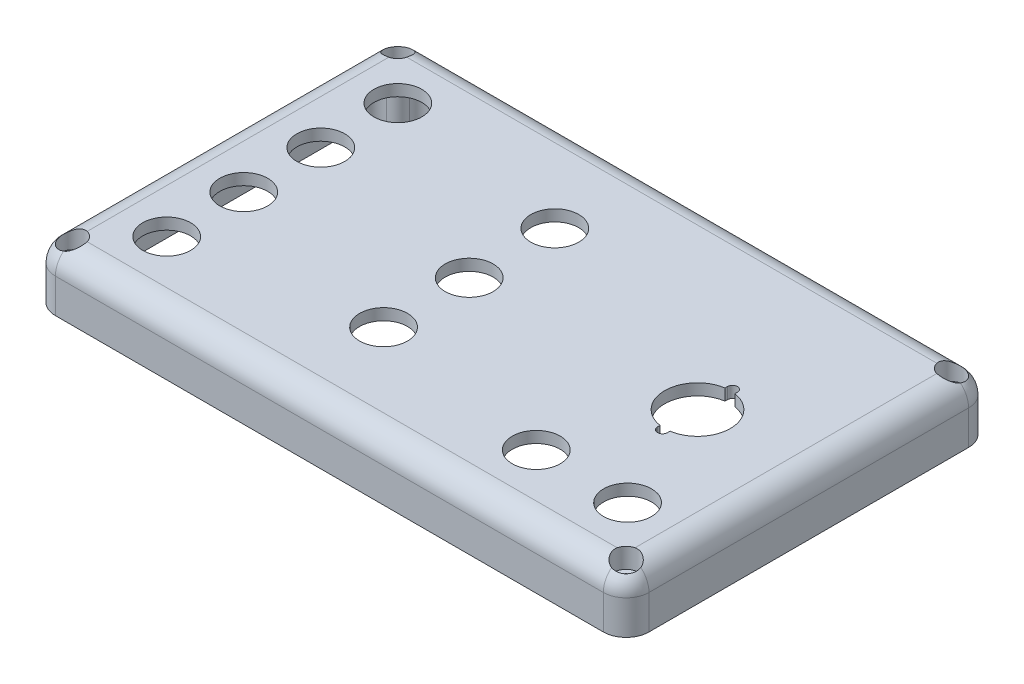
SolidWorks part; units mm, degrees
ref_plane "Front Plane" through (0, 0, 0) normal (0, 0, 1) x (1, 0, 0)
ref_plane "Top Plane" through (0, 0, 0) normal (0, 1, 0) x (1, 0, 0)
ref_plane "Right Plane" through (0, 0, 0) normal (1, 0, 0) x (0, 0, -1)
sketch "Sketch1" plane through (0, 0, 0) normal (0, 1, 0) x (1, 0, 0)
  line L0 (0, 112) -> (8, 112)
  line L1 (0, 0) -> (200, 0)
  line L2 (0, 0) -> (0, 120)
  line L3 (0, 120) -> (200, 120)
  line L4 (200, 0) -> (200, 120)
  line L5 (-4, 124) -> (204, 124)
  line L6 (-4, 124) -> (-4, -4)
  line L7 (-4, -4) -> (204, -4)
  line L8 (204, 124) -> (204, -4)
  line L9 (8, 112) -> (8, 120)
  line L10 (100, 120) -> (100, 0) construction
  line L11 (0, 60) -> (200, 60) construction
  line L12 (192, 112) -> (192, 120)
  line L13 (200, 112) -> (192, 112)
  line L14 (200, 8) -> (192, 8)
  line L15 (192, 8) -> (192, 0)
  line L16 (8, 8) -> (8, 0)
  line L17 (0, 8) -> (8, 8)
  line L18 (165, 60) -> (165, 0) construction
  line L19 (163.25, 71.3661) -> (163.25, 72.25)
  line L20 (166.75, 72.25) -> (166.75, 71.3661)
  line L21 (163.25, 48.6339) -> (163.25, 47.75)
  line L22 (166.75, 47.75) -> (166.75, 48.6339)
  circle A0 centre (19.5, 100.5) radius 8.4
  circle A1 centre (19.5, 73.5) radius 8.4
  circle A2 centre (19.5, 46.5) radius 8.4
  circle A3 centre (19.5, 19.5) radius 8.4
  circle A4 centre (85, 90) radius 8.4
  circle A5 centre (85, 60) radius 8.4
  circle A6 centre (85, 30) radius 8.4
  circle A9 centre (165, 60) radius 11.5
  circle A10 centre (149, 19.5) radius 8.4
  circle A11 centre (181, 19.5) radius 8.4
  circle A12 centre (165, 60) radius 16 construction
  arc A13 (163.25, 72.25) -> (166.75, 72.25) centre (165, 72.25) cw
  arc A14 (163.25, 47.75) -> (166.75, 47.75) centre (165, 47.75) ccw
  point P51 (165, 74)
  point P54 (165, 71.5)
  dimension "D9" = 16.8
  dimension "D13" = 16.8
  dimension "D19" = 23
  dimension "D21" = 16.8
  dimension "D22" = 32
  dimension "D1" = 200
  dimension "D2" = 120
  dimension "D3" = 4
  dimension "D4" = 4
  dimension "D5" = 4
  dimension "D6" = 4
  dimension "D7" = 8
  dimension "D8" = 8
  dimension "D11" = 23.5
  dimension "D12" = 23.5
  dimension "D15" = 30
  dimension "D16" = 30
  dimension "D17" = 27
  dimension "D18" = 85
  dimension "D20" = 35
  dimension "D23" = 32
  dimension "D24" = 2.5
  dimension "D25" = 3.5
  dimension "D10" = 4
  dimension "D14" = 3
extrude "Boss-Extrude1" add sketch "Sketch1" against normal blind 16 contours L8 L5 L6 L7 L4 L1 L2 L3 | L17 L2 L1 L16 | L14 L15 L1 L4 | L13 L4 L3 L12 | L0 L9 L3 L2 region at (4, 0, -116) region at (4, 0, -4) region at (196, 0, -116) region at (196, 0, -4) region at (100, 0, -121.5577)
extrude "Boss-Extrude2" add sketch "Sketch1<3>" along normal blind 4 contours L2 L17 L16 L1 L15 L14 L4 L13 L12 L3 L9 L0 A0 A1 A2 A3 A4 A5 A6 A9 A10 A11 | L8 L5 L6 L7 L4 L1 L2 L3 | L0 L9 L3 L2 | L17 L2 L1 L16 | L13 L4 L3 L12 | L14 L15 L1 L4 region at (4, 0, -116) region at (101.1513, 0, -60.8422) region at (4, 0, -4) region at (196, 0, -116) region at (196, 0, -4) region at (100, 0, -121.5577)
sketch "Sketch1<3>" plane through (0, 0, 0) normal (0, 1, 0) x (1, 0, 0) same geometry as "Sketch1"
hole_wizard "M4 Clearance Hole1" positions "Sketch2" profile "Sketch4" hole size "M4" standard "ISO" end condition through all
sketch "Sketch2" plane through (0, 4, 0) normal (0, 1, 0) x (1, 0, 0)
  line L1 (3, 117) -> (197, 117) construction
  line L2 (3, 117) -> (3, 3) construction
  line L3 (3, 3) -> (197, 3) construction
  line L4 (197, 117) -> (197, 3) construction
  line L5 (0, 0) -> (0, 120) construction
  line L6 (0, 120) -> (200, 120) construction
  point P0 (3, 117)
  point P1 (197, 3)
  point P184 (3, 3)
  point P185 (197, 117)
  dimension "D1" = 114
  dimension "D2" = 194
  dimension "D3" = 3
  dimension "D4" = 3
sketch "Sketch4" plane through (3, 4, -117) normal (1, 0, 0) x (0, 0, 1)
  line L0 (0, 0) -> (0, 20)
  line L1 (0, 20) -> (2.4, 20)
  line L2 (2.4, 20) -> (2.4, 0)
  line L5 (2.4, 0) -> (0, 0)
  line L11 (0, -6.35) -> (0, 107.95) construction
  dimension "Thru Hole Dia." = 4.8
  dimension "Thru Hole Depth" = 20
fillet "Fillet2" radius 8 4 edges at (-4, -6, -124) (-4, -6, 4) (204, -6, 4) (204, -6, -124)
fillet "Fillet1" radius 4 12 edges at (192, -8, 0) (192, -8, -8) (200, -8, -8) (8, -8, 0) (8, -8, -8) (0, -8, -8) (0, -8, -112) (8, -8, -120) (8, -8, -112) (192, -8, -120) (192, -8, -112) (200, -8, -112)
fillet "Fillet3" radius 8 8 edges at (-1.6569, 4, 1.6569) (-4, 4, -60) (-1.6569, 4, -121.6569) (100, 4, -124) (201.6569, 4, -121.6569) (204, 4, -60) (201.6569, 4, 1.6569) (100, 4, 4)
fillet "Fillet4" radius 3 16 edges at (9.1716, 0, -1.1716) (6.8284, 0, -6.8284) (1.1716, 0, -9.1716) (0, 0, -60) (1.1716, 0, -110.8284) (6.8284, 0, -113.1716) (9.1716, 0, -118.8284) (100, 0, -120) (190.8284, 0, -118.8284) (193.1716, 0, -113.1716) (198.8284, 0, -110.8284) (200, 0, -60) (198.8284, 0, -9.1716) (193.1716, 0, -6.8284) (190.8284, 0, -1.1716) (100, 0, 0)
sketch "Sketch8" plane through (0, 4, 0) normal (0, 1, 0) x (1, 0, 0)
  circle A0 centre (3, 117) radius 4.25
  circle A1 centre (197, 117) radius 4.25
  circle A2 centre (197, 3) radius 4.25
  circle A3 centre (3, 3) radius 4.25
  dimension "D1" = 8.5
extrude "Cut-Extrude1" cut sketch "Sketch8" against normal blind 7
equation "\"D4@Sketch1\"=\"D3@Sketch1\""
equation "\"D5@Sketch1\"=\"D3@Sketch1\""
equation "\"D6@Sketch1\"=\"D3@Sketch1\""
equation "\"D8@Sketch1\"=\"D7@Sketch1\""
equation "\"D11@Sketch1\"=\"D12@Sketch1\""
equation "\"D13@Sketch1\"=\"D9@Sketch1\""
equation "\"D21@Sketch1\"=\"D9@Sketch1\""
